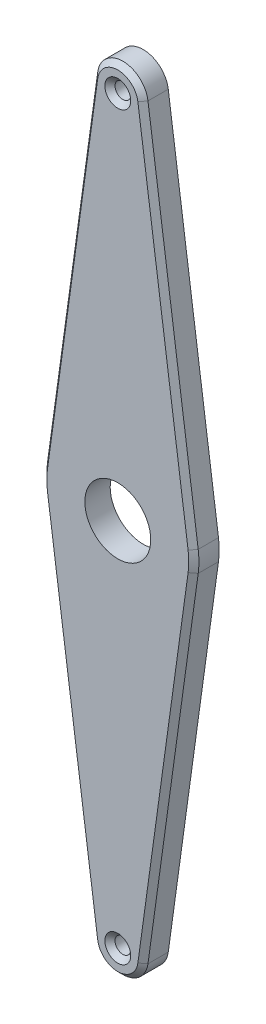
SolidWorks part; units mm, degrees
ref_plane "Front Plane" through (0, 0, 0) normal (0, 0, 1) x (1, 0, 0)
ref_plane "Top Plane" through (0, 0, 0) normal (0, 1, 0) x (1, 0, 0)
ref_plane "Right Plane" through (0, 0, 0) normal (1, 0, 0) x (0, 0, -1)
sketch "Sketch1" plane through (0, 0, 0) normal (0, 0, 1) x (1, 0, 0)
  line L1 (191, 68) -> (85, 68)
  line L2 (85, 68) -> (85, 141) construction
  line L3 (89.9529, 141.6849) -> (99.8586, 70.0548)
  line L8 (0, 136) -> (0, 0)
  line L9 (0, 0) -> (191, 0)
  line L10 (191, 0) -> (191, 136)
  line L11 (191, 136) -> (0, 136)
  line L12 (80.0471, 141.6849) -> (70.1414, 70.0548)
  line L13 (89.9529, -5.6849) -> (99.8586, 65.9452)
  line L14 (80.0471, -5.6849) -> (70.1414, 65.9452)
  circle A0 centre (85, 68) radius 15
  circle A1 centre (85, 141) radius 5
  circle A2 centre (85, -5) radius 5
  dimension "D2" = 30
  dimension "D4" = 10
  dimension "D3" = 5
extrude "Boss-Extrude1" add sketch "Sketch1" along normal blind 5 contours L2 A0 L3 L11 | A0 L2 L11 L12 | A1 | A1 L11 L3 | A1 L12 L11 | L1 L2 A0 | L2 L1 A0 | A0 L14 L9 L13 | L14 A2 L9 | L9 A2 L13 | A2 region at (82.8779, 65.8779, 0) region at (91.3662, 74.3662, 0) region at (90.3088, 104.3689, 0) region at (85, 31.6311, 0) region at (89.2502, -1.2971, 0) region at (89.2502, 137.2971, 0) region at (79.6912, 104.3689, 0) region at (80.7498, -1.2971, 0) region at (85, -5, 0) region at (89.8471, 141.3336, 0) region at (80.7498, 137.2971, 0)
chamfer "Chamfer1" distance 1 angle 45 8 edges at (75.0943, 30.1301, 5) (70, 68, 5) (75.0943, 105.8699, 5) (85, 146, 5) (94.9057, 105.8699, 5) (100, 68, 5) (94.9057, 30.1301, 5) (85, -10, 5)
sketch "Sketch6" plane through (0, 0, 5) normal (0, 0, 1) x (1, 0, 0)
  circle A0 centre (85, 141) radius 1.55
  dimension "D1" = 3.1
extrude "Cut-Extrude2" cut sketch "Sketch6" against normal up to next contours A0 region at (85, 141, 5)
chamfer "Chamfer3" distance 1 angle 45 1 edges at (86.55, 141, 5)
sketch "Sketch7" plane through (0, 0, 5) normal (0, 0, 1) x (1, 0, 0)
  line L1 (190.9943, 69.0969) -> (85, 68) construction
  line L2 (190.9943, 69.0969) -> (85, 68) construction
ref_axis "Axis2" through (99, 68, 5) along (-1, 0, 0)
sketch "Sketch8" plane through (0, 0, 0) normal (0, 0, -1) x (-1, 0, 0)
  line L0 (-100, 68) -> (-70, 68) construction
  arc A0 (-99.8586, 70.0548) -> (-99.8586, 65.9452) centre (-85, 68) ccw construction
  arc A1 (-70.1414, 65.9452) -> (-70.1414, 70.0548) centre (-85, 68) ccw construction
ref_axis "Axis3" through (100, 68, 0) along (-1, 0, 0)
ref_plane "Plane3" through (0, 68, 0) normal (0, -1, 0) x (-1, 0, 0)
mirror "Mirror2" about plane through (0, 68, 0) normal (0, -1, 0) of "Cut-Extrude2", "Chamfer3"
sketch "Sketch9" plane through (0, 0, 0) normal (0, 0, -1) x (-1, 0, 0)
  line L0 (-100, 68) -> (-70, 68) construction
  arc A0 (-99.8586, 70.0548) -> (-99.8586, 65.9452) centre (-85, 68) ccw construction
  arc A1 (-70.1414, 65.9452) -> (-70.1414, 70.0548) centre (-85, 68) ccw construction
  point P8 (-85, 68)
ref_point "Point1"
sketch "Sketch10" plane through (0, 0, 0) normal (0, 0, -1) x (-1, 0, 0)
  circle A0 centre (-85, 68) radius 6.5
  dimension "D1" = 13
extrude "Cut-Extrude3" cut sketch "Sketch10" against normal up to next
